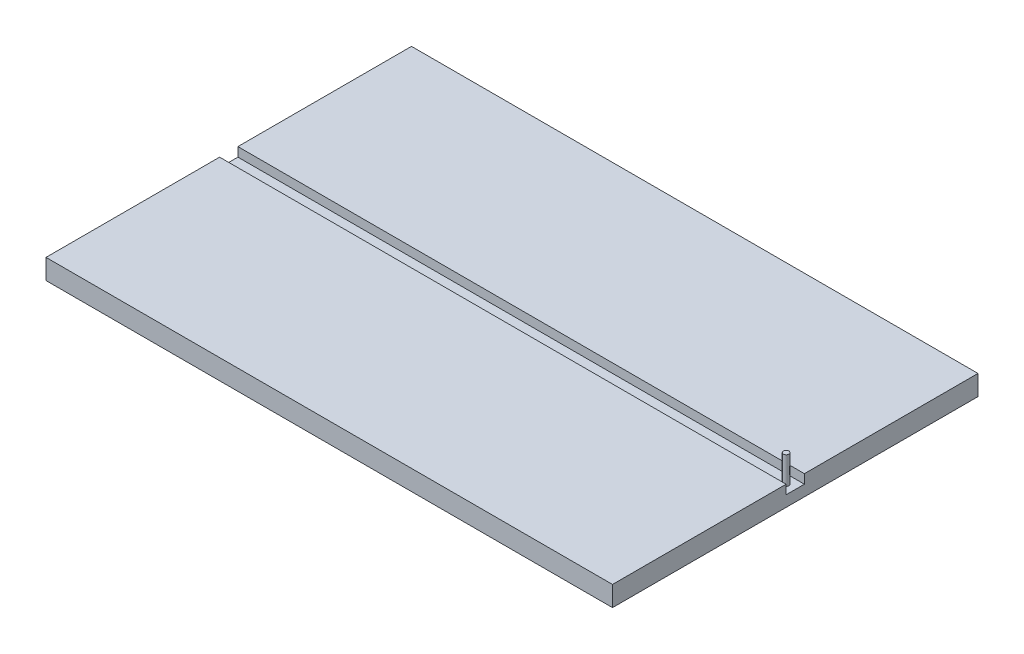
SolidWorks part; units mm, degrees
material "PBT General Purpose"
ref_plane "Front Plane" through (0, 0, 0) normal (0, 0, 1) x (1, 0, 0)
ref_plane "Top Plane" through (0, 0, 0) normal (0, 1, 0) x (1, 0, 0)
ref_plane "Right Plane" through (0, 0, 0) normal (1, 0, 0) x (0, 0, -1)
sketch "Sketch1" plane through (0, 0, 0) normal (0, 1, 0) x (1, 0, 0)
  line L1 (0, 0) -> (310, 0)
  line L2 (0, 0) -> (0, 200)
  line L3 (0, 200) -> (310, 200)
  line L4 (310, 0) -> (310, 200)
  dimension "D1" = 310
extrude "Boss-Extrude1" add sketch "Sketch1" along normal blind 6
sketch "Sketch2" plane through (0, 6, 0) normal (0, 1, 0) x (1, 0, 0)
  line L0 (310, 0) -> (310, 200) construction
  line L1 (0, 0) -> (310, 0)
  line L2 (0, 0) -> (0, 95)
  line L3 (0, 95) -> (310, 95)
  line L4 (310, 0) -> (310, 95)
  line L6 (0, 200) -> (310, 200)
  line L7 (0, 200) -> (0, 105)
  line L8 (0, 105) -> (310, 105)
  line L9 (310, 200) -> (310, 105)
extrude "Boss-Extrude2" add sketch "Sketch2" along normal blind 5
sketch "Sketch3" plane through (0, 6, 0) normal (0, 1, 0) x (1, 0, 0)
  line L0 (0, 105) -> (310, 105) construction
  line L1 (310, 95) -> (310, 105) construction
  circle A0 centre (305, 100) radius 1.5
  dimension "D1" = 5
  dimension "D2" = 5
extrude "Boss-Extrude3" add sketch "Sketch3" along normal blind 15
